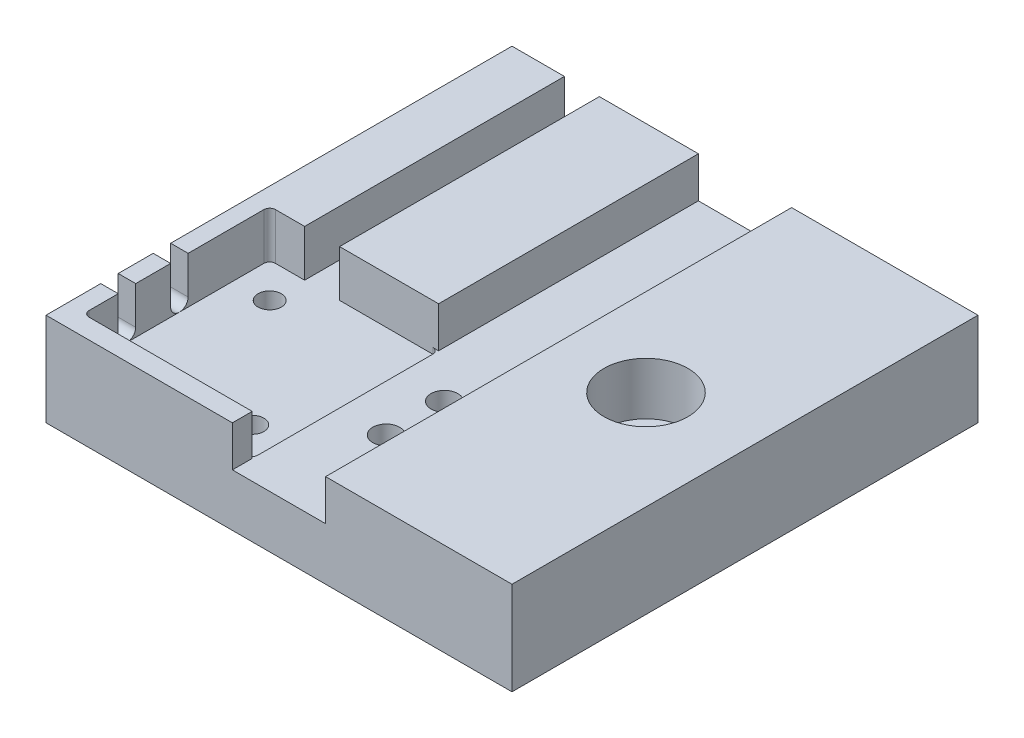
SolidWorks part; units mm, degrees
ref_plane "前视基准面" through (0, 0, 0) normal (0, 0, 1) x (1, 0, 0)
ref_plane "上视基准面" through (0, 0, 0) normal (0, 1, 0) x (1, 0, 0)
ref_plane "右视基准面" through (0, 0, 0) normal (1, 0, 0) x (0, 0, -1)
other "Configuration Table"
sketch "草图1" plane through (0, 0, 0) normal (0, 1, 0) x (1, 0, 0)
  line L1 (0, 0) -> (40, 0)
  line L2 (0, 0) -> (0, -40)
  line L3 (0, -40) -> (40, -40)
  line L4 (40, 0) -> (40, -40)
  dimension "D1" = 40
  dimension "D2" = 40
extrude "凸台-拉伸1" add sketch "草图1" along normal blind 8
sketch "草图2" plane through (0, 8, 0) normal (0, 1, 0) x (1, 0, 0)
  line L0 (40, 0) -> (0, 0) construction
  line L1 (16, 0) -> (24, 0)
  line L2 (16, 0) -> (16, -40)
  line L3 (16, -40) -> (24, -40)
  line L4 (24, 0) -> (24, -40)
  line L5 (0, -40) -> (40, -40) construction
  line L6 (0, -20) -> (16, -20) construction
  line L7 (0, 0) -> (0, -40) construction
  line L8 (24, -20) -> (40, -20) construction
  line L9 (40, -40) -> (40, 0) construction
  dimension "D1" = 8
  dimension "D2" = 16
extrude "切除-拉伸1" cut sketch "草图2" against normal blind 3.5
sketch "草图3" plane through (0, 0, 0) normal (0, -1, 0) x (-1, 0, 0)
  line L0 (-16, -39) -> (-24, -39) construction
  line L1 (-16, 0) -> (-16, -40) construction
  line L2 (-24, -40) -> (-24, 0) construction
  line L3 (-20, -39) -> (-20, -30.8) construction
  line L4 (-20, -30.8) -> (-20, -25.8) construction
  line L5 (-16, -1) -> (-24, -1) construction
  line L6 (0, -40) -> (-40, -40) construction
  line L7 (-40, 0) -> (0, 0) construction
  line L8 (-20, -25.8) -> (-20, -1) construction
  circle A0 centre (-20, -30.8) radius 1.15
  circle A1 centre (-20, -25.8) radius 1.15
  dimension "D4" = 2.3
  dimension "D1" = 5
  dimension "D2" = 1
  dimension "D3" = 1
  dimension "D5" = 8.2
extrude "切除-拉伸2" cut sketch "草图3" against normal through all
sketch "草图4" plane through (0, 0, 0) normal (0, -1, 0) x (-1, 0, 0)
  circle A0 centre (-20, -30.8) radius 2
  circle A1 centre (-20, -25.8) radius 2
  dimension "D1" = 4
extrude "切除-拉伸3" cut sketch "草图4" against normal blind 2.4
sketch "草图5" plane through (0, 8, 0) normal (0, 1, 0) x (1, 0, 0)
  line L0 (16, 0) -> (16, -40) construction
  line L1 (16, -22.3) -> (1.5, -22.3)
  line L2 (16, -22.3) -> (16, -38.3)
  line L3 (16, -38.3) -> (1.5, -38.3)
  line L4 (1.5, -22.3) -> (1.5, -38.3)
  line L6 (20, -25.8) -> (20, -30.8) construction
  line L7 (20, -28.3) -> (50020, -28.3) construction
  line L8 (0, 0) -> (0, -40) construction
  point P14 (20, -28.3)
  dimension "D1" = 6
  dimension "D2" = 10
  dimension "D3" = 14.5
  dimension "D4" = 1.5
extrude "切除-拉伸4" cut sketch "草图5" against normal blind 4
fillet "圆角2" radius 0.5 4 edges at (16, 4.25, 38.3) (16, 4.25, 22.3) (1.5, 6, 38.3) (1.5, 6, 22.3)
sketch "草图6" plane through (0, 8, 0) normal (0, 1, 0) x (1, 0, 0)
  line L0 (0, 0) -> (0, -40) construction
  line L1 (0, -33.8) -> (1.5, -33.8)
  line L2 (0, -33.8) -> (0, -35.3)
  line L3 (0, -35.3) -> (1.5, -35.3)
  line L4 (1.5, -33.8) -> (1.5, -35.3)
  line L5 (1.5, -22.8) -> (1.5, -37.8) construction
  line L6 (2, -38.3) -> (16, -38.3) construction
  line L7 (0, -29.3) -> (1.5, -29.3)
  line L8 (0, -29.3) -> (0, -30.8)
  line L9 (0, -30.8) -> (1.5, -30.8)
  line L10 (1.5, -29.3) -> (1.5, -30.8)
  dimension "D1" = 1.5
  dimension "D2" = 1.5
  dimension "D3" = 3
  dimension "D4" = 3
extrude "切除-拉伸5" cut sketch "草图6" against normal blind 4
sketch "草图7" plane through (0, 4, 0) normal (0, 1, 0) x (1, 0, 0)
  line L0 (16, -22.3) -> (2, -22.3) construction
  line L1 (1.5, -22.8) -> (1.5, -29.3) construction
  line L2 (2, -38.3) -> (15.5, -38.3) construction
  line L3 (16, -37.8) -> (16, -22.8) construction
  circle A4 centre (4.5, -25.3) radius 1
  circle A5 centre (13, -35.3) radius 1
  circle A6 centre (4.5, -25.3) radius 2 construction
  circle A7 centre (13, -35.3) radius 2 construction
  dimension "D1" = 2
  dimension "D6" = 4
  dimension "D7" = 4
  dimension "D2" = 3
  dimension "D3" = 3
  dimension "D4" = 3
  dimension "D5" = 3
extrude "切除-拉伸6" cut sketch "草图7" against normal blind 4
fillet "圆角3" 2 edges at (0.75, 4, 29.3) (0.75, 4, 30.8) type full round first side face at (0.75, 6, 29.3) second side face at (0.75, 6, 30.8) middle face at (4.5, 4, 26.3)
fillet "圆角4" 2 edges at (0.75, 4, 33.8) (0.75, 4, 35.3) type full round first side face at (0.75, 6, 33.8) second side face at (0.75, 6, 35.3) middle face at (4.5, 4, 26.3)
sketch "草图8" plane through (0, 8, 0) normal (0, 1, 0) x (1, 0, 0)
  line L0 (6, 0.4155) -> (6, -29.1559) construction
  line L1 (7.5, 0.4155) -> (7.5, -29.1559)
  line L2 (4.5, 0.4155) -> (4.5, -29.1559)
  line L3 (0, 0) -> (0, -29.3) construction
  arc A0 (7.5, 0.4155) -> (4.5, 0.4155) centre (6, 0.4155) ccw
  arc A1 (4.5, -29.1559) -> (7.5, -29.1559) centre (6, -29.1559) ccw
  point P2 (6, -14.3702)
  dimension "D2" = 1.5
  dimension "D1" = 4.5
extrude "切除-拉伸7" cut sketch "草图8" against normal blind 4
sketch "草图10" plane through (0, 8, 0) normal (0, 1, 0) x (1, 0, 0)
  line L0 (31.5, -20) -> (40, -20) construction
  line L1 (40, -40) -> (40, 0) construction
  circle A0 centre (31.5, -20) radius 3.6
  dimension "D2" = 7.2
  dimension "D1" = 8.5
extrude "切除-拉伸9" cut sketch "草图10" against normal blind 4.5
sketch "草图11" plane through (0, 3.5, 0) normal (0, 1, 0) x (1, 0, 0)
  circle A0 centre (31.5, -20) radius 2.1
  dimension "D1" = 4.2
extrude "切除-拉伸10" cut sketch "草图11" against normal through all
